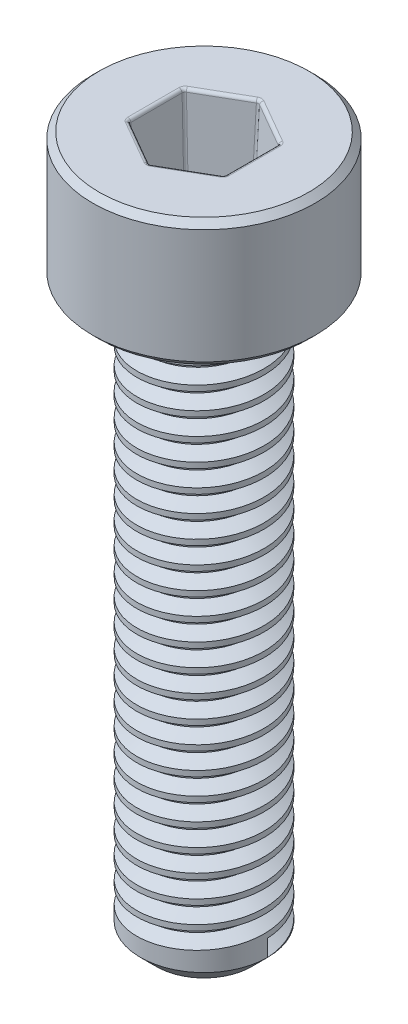
SolidWorks part; units mm, degrees
ref_plane "Спереди" through (0, 0, 0) normal (0, 0, 1) x (1, 0, 0)
ref_plane "Сверху" through (0, 0, 0) normal (0, 1, 0) x (1, 0, 0)
ref_plane "Справа" through (0, 0, 0) normal (1, 0, 0) x (0, 0, -1)
sketch "Эскиз1" plane through (0, 0, 0) normal (0, 1, 0) x (1, 0, 0)
  circle A0 centre (0, 0) radius 3.5
  dimension "D1" = 7
extrude "Бобышка-Вытянуть1" add sketch "Эскиз1" along normal blind 4
sketch "Эскиз2" plane through (0, 4, 0) normal (0, 1, 0) x (1, 0, 0)
  line L1 (0, 1.7321) -> (-1.5, 0.866)
  line L2 (-1.5, 0.866) -> (-1.5, -0.866)
  line L3 (-1.5, -0.866) -> (0, -1.7321)
  line L4 (0, -1.7321) -> (1.5, -0.866)
  line L5 (1.5, -0.866) -> (1.5, 0.866)
  line L6 (1.5, 0.866) -> (0, 1.7321)
  circle A0 centre (0, 0) radius 1.5 construction
extrude "Вырез-Вытянуть1" cut sketch "Эскиз2" against normal blind 3 draft 3
fillet "Скругление1" radius 0.1 18 edges at (0.75, 4, -1.299) (-0.75, 4, -1.299) (1.5, 4, 0) (-1.5, 4, 0) (0.75, 4, 1.299) (1.3428, 1, 0) (0.6714, 1, 1.1629) (-0.6714, 1, 1.1629) (-1.3428, 1, 0) (-0.6714, 1, -1.1629) (0.6714, 1, -1.1629) (-0.75, 4, 1.299) (-1.4214, 2.5, 0.8206) (0, 2.5, 1.6413) (1.4214, 2.5, 0.8206) (1.4214, 2.5, -0.8206) (0, 2.5, -1.6413) (-1.4214, 2.5, -0.8206)
chamfer "Фаска1" distance 0.2 angle 45 2 edges at (0, 0, 3.5) (0, 4, 3.5)
sketch "Эскиз3" plane through (0, 0, 0) normal (0, -1, 0) x (1, 0, 0)
  circle A0 centre (0, 0) radius 2
  dimension "D1" = 4
extrude "Бобышка-Вытянуть2" add sketch "Эскиз3" along normal blind 18
chamfer "Фаска2" distance 0.5 angle 45 1 edges at (0, -18, -2)
thread "Резьба1" pitch 0.7 method cut profile "Профиль резьбы1" start angle 0, offset 0, length 0, pitch 0.7, diameter 4
ref_plane "Плоскость1" through (2, -17.5, 0) normal (0, 0, -1) x (-1, 0, 0)
sketch "Профиль резьбы1" plane through (2, -17.5, 0) normal (0, 0, -1) x (-1, 0, 0)
  line L0 (0, 0) -> (0, 0.7) construction
  line L1 (0, 0) -> (0.3789, 0.2187)
  line L2 (0.3789, 0.2187) -> (0.3789, 0.3062)
  line L3 (0.3789, 0.3062) -> (0, 0.525)
  line L4 (0.3789, 0.2625) -> (0, 0.2625) construction
  line L11 (0, 0) -> (0, 0.525)
  point P2 (0, 0)
  dimension "Pitch" = 0.7
  dimension "Profile_Angle" = 60
  dimension "Profile_Land" = 0.0875
  dimension "Profile_Height" = 0.3789
sketch "Эскиз4" plane through (0, 4, 0) normal (0, 1, 0) x (1, 0, 0)
  circle A0 centre (0, 0) radius 3.6785 construction
  circle A1 centre (0, 3.6785) radius 0.2185
  circle A2 centre (0.5754, 3.6332) radius 0.2185
  circle A3 centre (1.1367, 3.4985) radius 0.2185
  circle A4 centre (1.67, 3.2776) radius 0.2185
  circle A5 centre (2.1622, 2.976) radius 0.2185
  circle A6 centre (2.6011, 2.6011) radius 0.2185
  circle A7 centre (2.976, 2.1622) radius 0.2185
  circle A8 centre (3.2776, 1.67) radius 0.2185
  circle A9 centre (3.4985, 1.1367) radius 0.2185
  circle A10 centre (3.6332, 0.5754) radius 0.2185
  circle A11 centre (3.6785, 0) radius 0.2185
  circle A12 centre (3.6332, -0.5754) radius 0.2185
  circle A13 centre (3.4985, -1.1367) radius 0.2185
  circle A14 centre (3.2776, -1.67) radius 0.2185
  circle A15 centre (2.976, -2.1622) radius 0.2185
  circle A16 centre (2.6011, -2.6011) radius 0.2185
  circle A17 centre (2.1622, -2.976) radius 0.2185
  circle A18 centre (1.67, -3.2776) radius 0.2185
  circle A19 centre (1.1367, -3.4985) radius 0.2185
  circle A20 centre (0.5754, -3.6332) radius 0.2185
  circle A21 centre (0, -3.6785) radius 0.2185
  circle A22 centre (-0.5754, -3.6332) radius 0.2185
  circle A23 centre (-1.1367, -3.4985) radius 0.2185
  circle A24 centre (-1.67, -3.2776) radius 0.2185
  circle A25 centre (-2.1622, -2.976) radius 0.2185
  circle A26 centre (-2.6011, -2.6011) radius 0.2185
  circle A27 centre (-2.976, -2.1622) radius 0.2185
  circle A28 centre (-3.2776, -1.67) radius 0.2185
  circle A29 centre (-3.4985, -1.1367) radius 0.2185
  circle A30 centre (-3.6332, -0.5754) radius 0.2185
  circle A31 centre (-3.6785, 0) radius 0.2185
  circle A32 centre (-3.6332, 0.5754) radius 0.2185
  circle A33 centre (-3.4985, 1.1367) radius 0.2185
  circle A34 centre (-3.2776, 1.67) radius 0.2185
  circle A35 centre (-2.976, 2.1622) radius 0.2185
  circle A36 centre (-2.6011, 2.6011) radius 0.2185
  circle A37 centre (-2.1622, 2.976) radius 0.2185
  circle A38 centre (-1.67, 3.2776) radius 0.2185
  circle A39 centre (-1.1367, 3.4985) radius 0.2185
  circle A40 centre (-0.5754, 3.6332) radius 0.2185
  point P85 (0, 0)
  dimension "D1" = 40
extrude "Вырез-Вытянуть2" [suppressed] cut sketch "Эскиз4" against normal blind 3 from offset 0.15 offset against normal yes
